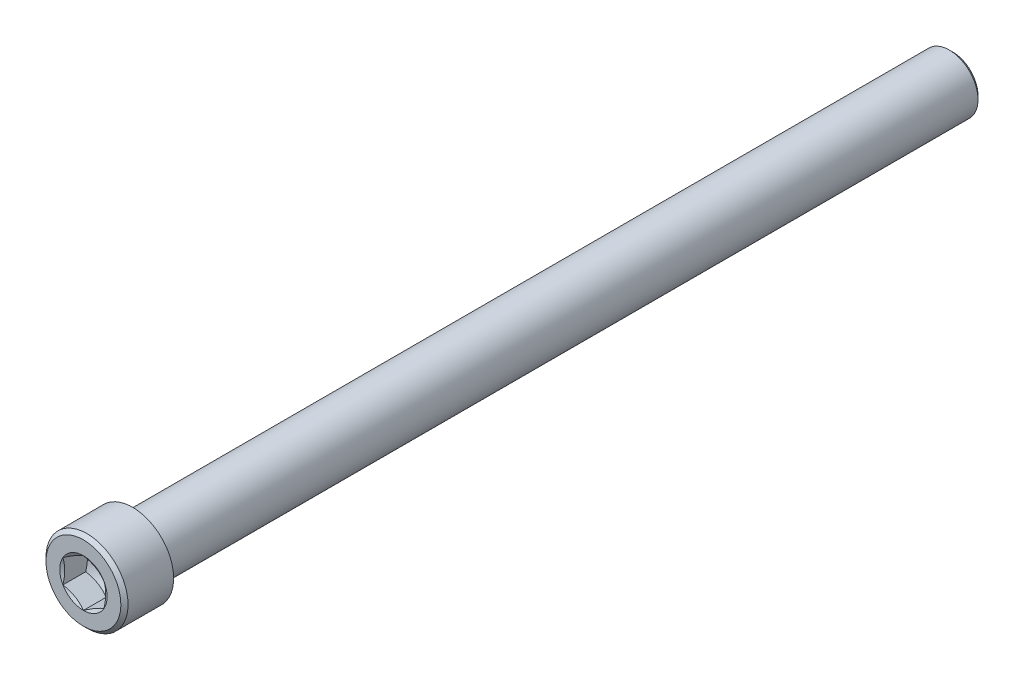
SolidWorks part; units mm, degrees
ref_plane "Front" through (0, 0, 0) normal (0, 0, 1) x (1, 0, 0)
ref_plane "Top" through (0, 0, 0) normal (0, 1, 0) x (1, 0, 0)
ref_plane "Right" through (0, 0, 0) normal (1, 0, 0) x (0, 0, -1)
sketch "Sketch1" plane through (0, 0, 0) normal (1, 0, 0) x (0, 0, -1)
  line L0 (0, 10) -> (-12, 10)
  line L1 (-12, 10) -> (-12, 0)
  line L2 (-12, 0) -> (200, 0)
  line L3 (200, 0) -> (200, 7)
  line L4 (200, 7) -> (0, 7)
  line L5 (0, 7) -> (0, 10)
  line L6 (0, 0) -> (12.7561, 0) construction
  dimension "l" = 200
  dimension "d" = 14
  dimension "k" = 12
  dimension "dk" = 20
revolve "Revolve1" add sketch "Sketch1" angle 360 about L2
cosmetic thread "Filettatura cosmetica1" parameters "D2"=11.797
sketch "Sketch7" plane through (0, 0, 0) normal (1, 0, 0) x (0, 0, -1)
  line L0 (-6.6396, 0) -> (3.6195, 0) construction
  line L1 (-12, 0) -> (-12, 5)
  line L2 (-12, 10) -> (-12, -10) construction
  line L3 (-12, 5) -> (-6, 5)
  line L4 (-6, 5) -> (-3.1132, 0)
  line L6 (-12, 0) -> (-3.1132, 0)
  dimension "D1" = 60
  dimension "S" = 10
  dimension "t" = 6
revolve "Cut-Revolve2" cut sketch "Sketch7" angle 360 about L6
chamfer "Chamfer1" distance 0.875 2 edges at (0, -7, -200) (0, -10, 12)
sketch "Sketch8" plane through (0, 0, 12) normal (0, 0, 1) x (1, 0, 0)
  line L1 (0, 5.7735) -> (-5, 2.8868)
  line L2 (-5, 2.8868) -> (-5, -2.8868)
  line L3 (-5, -2.8868) -> (0, -5.7735)
  line L4 (0, -5.7735) -> (5, -2.8868)
  line L5 (5, -2.8868) -> (5, 2.8868)
  line L6 (5, 2.8868) -> (0, 5.7735)
  circle A0 centre (0, 0) radius 5 construction
  circle A1 centre (0, 0) radius 5 construction
extrude "Cut-Extrude1" cut sketch "Sketch8" against normal up to surface (5.5534 mm away) up to face at (5, 0, 6)
sketch "Sketch9" plane through (0, 0, 0) normal (1, 0, 0) x (0, 0, -1)
  line L0 (-12, 5) -> (4.2695, 5) construction
  line L3 (-12.5, 6.6395) -> (-12.5, 5)
  line L4 (-12.5, 5) -> (-11.5534, 5)
  line L5 (-11.5534, 5) -> (-12.5, 6.6395)
  line L6 (-12, 10) -> (-12, -10) construction
  dimension "D1" = 60
  dimension "D2" = 0.5
revolve "Cut-Revolve3" cut sketch "Sketch9" angle 360 about axis through (0, 0, 12) along (0, 0, -1)
fillet "Fillet2" radius 0.6 1 edges at (0, -7, 0)
